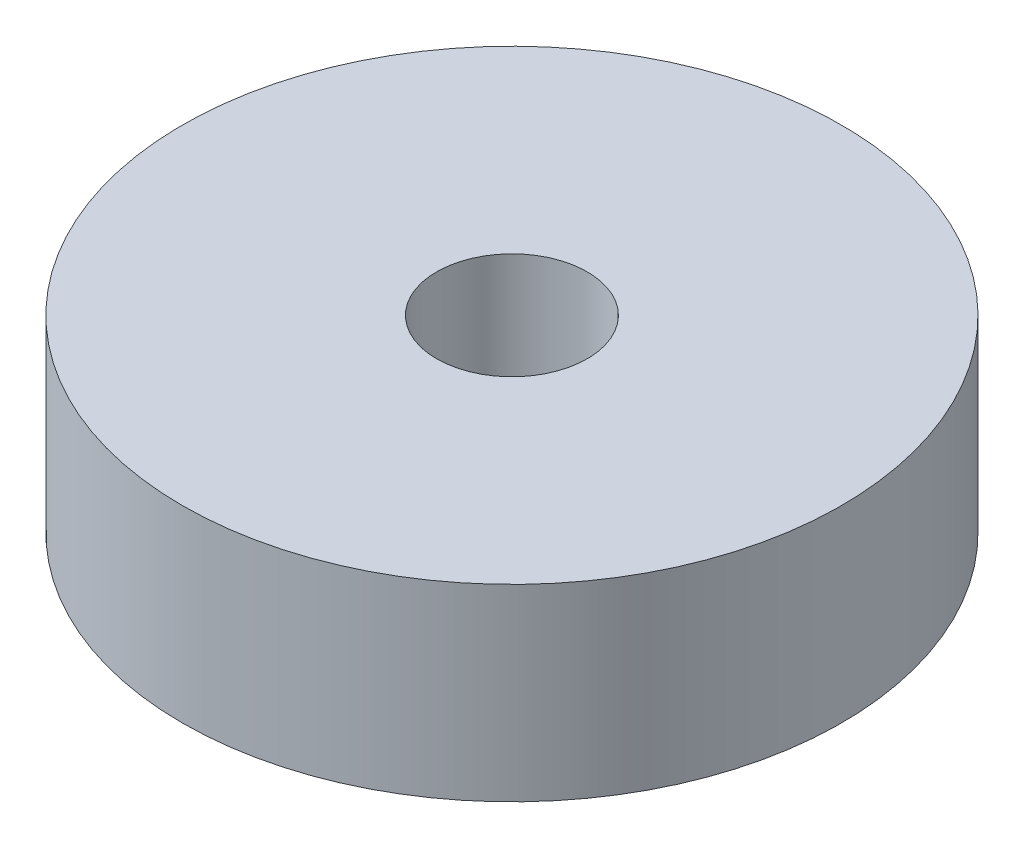
SolidWorks part; units mm, degrees
ref_plane "Front Plane" through (0, 0, 0) normal (0, 0, 1) x (1, 0, 0)
ref_plane "Top Plane" through (0, 0, 0) normal (0, 1, 0) x (1, 0, 0)
ref_plane "Right Plane" through (0, 0, 0) normal (1, 0, 0) x (0, 0, -1)
sketch "Sketch1" plane through (0, 0, 0) normal (0, 1, 0) x (1, 0, 0)
  circle A0 centre (0, 0) radius 17.5
  circle A1 centre (0, 0) radius 4
  dimension "D1" = 8
  dimension "D2" = 35
extrude "Boss-Extrude1" add sketch "Sketch1" along normal blind 10
sketch "Sketch3" plane through (0, 0, 0) normal (0, 1, 0) x (1, 0, 0)
  line L5 (-8.5, 3.3205) -> (-8.5, -3.3205)
  line L6 (-14.5, 3.3205) -> (-14.5, -3.3205)
  arc A3 (-14.5, 3.3205) -> (-8.5, 3.3205) centre (-11.5, 0) cw
  arc A4 (-14.5, -3.3205) -> (-8.5, -3.3205) centre (-11.5, 0) ccw
  point P4 (0, 0)
  point P6 (0, 0)
  point P10 (6.0667, -2.3624)
  point P13 (13.1917, -2.1619)
  point P16 (5.1401, -1.6006)
  point P17 (12.6382, -1.2398)
  dimension "D3" = 11.5
  dimension "D2" = 4.475
  dimension "D1" = 6
extrude "Cut-Extrude1" cut sketch "Sketch3" along normal blind 7
ref_plane "Plane1" through (-14.5, 0, 0) normal (1, 0, 0) x (0, 0, -1)
sketch "Sketch4" plane through (-14.5, 0, 0) normal (1, 0, 0) x (0, 0, -1)
  line L0 (3.3205, 0) -> (-3.3205, 0) construction
  circle A0 centre (0, 3) radius 2.125
  dimension "D1" = 3
  dimension "D2" = 4.25
extrude "Cut-Extrude2" cut sketch "Sketch4" against normal through all
